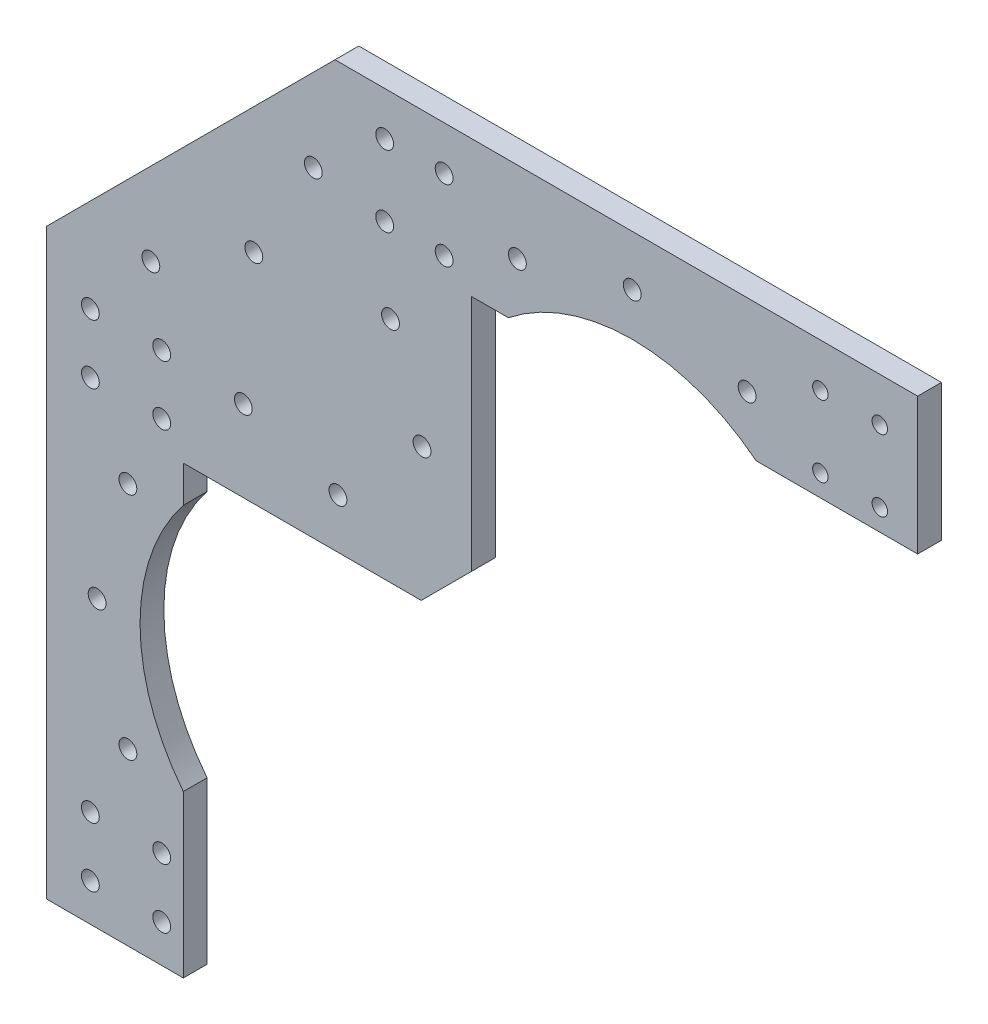
SolidWorks part; units mm, degrees
ref_plane "Front Plane" through (0, 0, 0) normal (0, 0, 1) x (1, 0, 0)
ref_plane "Top Plane" through (0, 0, 0) normal (0, 1, 0) x (1, 0, 0)
ref_plane "Right Plane" through (0, 0, 0) normal (1, 0, 0) x (0, 0, -1)
sketch "Sketch1" plane through (0, 0, 0) normal (0, 0, 1) x (1, 0, 0)
  line L0 (0, 0) -> (0, 75.5) construction
  line L1 (-98.5, -48) -> (-75.5, -48)
  line L2 (-98.5, -48) -> (-98.5, 49.9924)
  line L4 (-75.5, -48) -> (-75.5, 27) construction
  line L5 (-49.9924, 98.5) -> (48, 98.5)
  line L7 (-27, 75.5) -> (48, 75.5) construction
  line L8 (48, 98.5) -> (48, 75.5)
  line L9 (0, 0) -> (-75.5, 0) construction
  line L10 (-27, 75.5) -> (-75.5, 27) construction
  line L11 (-75.5, 75.5) -> (-27, 75.5) construction
  line L12 (-75.5, 27) -> (-75.5, 75.5) construction
  line L13 (-49.9924, 98.5) -> (-98.5, 49.9924)
  line L14 (-98.5, 98.5) -> (-49.9924, 98.5) construction
  line L15 (-98.5, 49.9924) -> (-98.5, 98.5) construction
  line L16 (-20.8425, 75.5) -> (-27, 75.5)
  line L17 (20.8425, 75.5) -> (48, 75.5)
  line L18 (-75.5, 27) -> (-75.5, 20.8425)
  line L19 (-75.5, -48) -> (-75.5, -20.8425)
  line L20 (-75.5, 20.8425) -> (-75.5, -20.8425) construction
  line L21 (-20.8425, 75.5) -> (20.8425, 75.5) construction
  line L22 (-75.5, 27) -> (-35.4853, 27)
  line L23 (-27, 35.4853) -> (-27, 75.5)
  line L24 (-35.4853, 27) -> (-27, 35.4853)
  arc A0 (20.8425, 75.5) -> (-20.8425, 75.5) centre (0, 49.3) ccw
  arc A1 (-75.5, 20.8425) -> (-75.5, -20.8425) centre (-49.3, 0) ccw
  point P16 (0, 0)
  dimension "D6" = 33.4791
  dimension "D1" = 135
  dimension "D2" = 23
  dimension "D3" = 75.5
  dimension "D4" = 48
  dimension "D8" = 27
  dimension "D9" = 12
  dimension "D5" = 97.9924
  dimension "D7" = 26.2
extrude "Boss-Extrude1" add sketch "Sketch1" along normal blind 4
ref_axis "Axis1" through (0, 0, -0.2) along (0, 0, 1)
sketch "Sketch3" plane through (0, 0, 4) normal (0, 0, 1) x (1, 0, 0)
  line L0 (-91.1351, 41.6359) -> (-91.1351, 31.6359) construction
  line L1 (-91.1351, -31.6359) -> (-91.1351, -41.6359) construction
  line L2 (-91.1351, -31.6359) -> (-79.1351, -31.6359) construction
  line L3 (-79.1351, -31.6359) -> (-79.1351, -41.6359) construction
  line L4 (-91.1351, -41.6359) -> (-79.1351, -41.6359) construction
  line L5 (-91.1351, 41.6359) -> (-79.1351, 41.6359) construction
  line L6 (-79.1351, 41.6359) -> (-79.1351, 31.6359) construction
  line L7 (-91.1351, 31.6359) -> (-79.1351, 31.6359) construction
  line L8 (31.6359, 91.1351) -> (31.6359, 79.1351) construction
  line L9 (31.6359, 91.1351) -> (41.6359, 91.1351) construction
  line L10 (41.6359, 91.1351) -> (41.6359, 79.1351) construction
  line L11 (31.6359, 79.1351) -> (41.6359, 79.1351) construction
  line L12 (-31.6359, 91.1351) -> (-31.6359, 79.1351) construction
  line L13 (-31.6359, 91.1351) -> (-41.6359, 91.1351) construction
  line L14 (-41.6359, 91.1351) -> (-41.6359, 79.1351) construction
  line L15 (-31.6359, 79.1351) -> (-41.6359, 79.1351) construction
  line L16 (-79.1351, 31.6359) -> (-79.1351, 0) construction
  line L17 (-79.1351, 0) -> (0, 0) construction
  line L18 (-79.1351, 0) -> (-79.1351, -31.6359) construction
  line L19 (0, 79.1351) -> (0, 0) construction
  line L20 (-31.6359, 79.1351) -> (0, 79.1351) construction
  line L21 (0, 79.1351) -> (31.6359, 79.1351) construction
  circle A0 centre (-91.1351, -41.6359) radius 1.5
  circle A1 centre (-91.1351, -31.6359) radius 1.5
  circle A2 centre (-79.1351, -31.6359) radius 1.5
  circle A3 centre (-79.1351, -41.6359) radius 1.5
  circle A4 centre (-91.1351, 31.6359) radius 1.5
  circle A5 centre (-91.1351, 41.6359) radius 1.5
  circle A6 centre (-79.1351, 41.6359) radius 1.5
  circle A7 centre (-79.1351, 31.6359) radius 1.5
  circle A8 centre (31.6359, 79.1351) radius 1.3
  circle A9 centre (31.6359, 91.1351) radius 1.3
  circle A10 centre (41.6359, 91.1351) radius 1.3
  circle A11 centre (41.6359, 79.1351) radius 1.3
  circle A12 centre (-31.6359, 79.1351) radius 1.5
  circle A13 centre (-31.6359, 91.1351) radius 1.5
  circle A14 centre (-41.6359, 91.1351) radius 1.5
  circle A15 centre (-41.6359, 79.1351) radius 1.5
  point P15 (0, 0)
  point P44 (0, 0)
  point P45 (0, 0)
  point P46 (0, 0)
  point P47 (0, 0)
  point P48 (-0.9577, 0)
  point P49 (0, 0)
  dimension "D1" = 3
  dimension "D2" = 3
  dimension "D3" = 2.6
  dimension "D4" = 3
  dimension "D5" = 79.1351
  dimension "D6" = 12
  dimension "D7" = 10
  dimension "D8" = 31.6359
extrude "Cut-Extrude1" cut sketch "Sketch3" against normal blind 10
sketch "Sketch4" plane through (0, 0, 4) normal (0, 0, 1) x (1, 0, 0)
  line L0 (0, 0) -> (0, 90) construction
  line L1 (0, 0) -> (-63.6396, 63.6396) construction
  line L2 (0, 0) -> (-90, 0) construction
  line L3 (-84.8236, 19.3185) -> (-90, 0) construction
  line L4 (-90, 0) -> (-84.8236, -19.3185) construction
  line L5 (-80.9601, 53.6396) -> (-63.6396, 63.6396) construction
  line L6 (-63.6396, 63.6396) -> (-83.2677, 83.2677) construction
  line L7 (-19.3185, 84.8236) -> (0, 90) construction
  line L8 (-65.4074, 40.6586) -> (-40.6586, 65.4074) construction
  line L9 (-35.3553, 49.4975) -> (-49.4975, 35.3553) construction
  line L10 (-75.5, -48) -> (-75.5, -20.8425) construction
  line L11 (-35.4853, 27) -> (-27, 35.4853) construction
  circle A0 centre (-90, 0) radius 1.5
  circle A1 centre (-63.6396, 63.6396) radius 1.5
  circle A2 centre (0, 90) radius 1.5
  circle A3 centre (-80.9601, 53.6396) radius 1.5
  circle A4 centre (-53.6396, 80.9601) radius 1.5
  circle A5 centre (19.3185, 84.8236) radius 1.5
  circle A6 centre (-19.3185, 84.8236) radius 1.5
  circle A7 centre (-84.8236, 19.3185) radius 1.5
  circle A8 centre (-84.8236, -19.3185) radius 1.5
  circle A9 centre (-40.6586, 65.4074) radius 1.5
  circle A10 centre (-65.4074, 40.6586) radius 1.5
  circle A11 centre (-49.4975, 35.3553) radius 1.5
  circle A12 centre (-35.3553, 49.4975) radius 1.5
  point P33 (-83.2677, 83.2677)
  dimension "D2" = 3
  dimension "D1" = 45
  dimension "D3" = 14.5
  dimension "D4" = 75
  dimension "D5" = 20
  dimension "D6" = 45.8162
  dimension "D7" = 75
  dimension "D8" = 75
  dimension "D9" = 35
  dimension "D10" = 20
  dimension "D11" = 15
  dimension "D12" = 15
extrude "Cut-Extrude2" cut sketch "Sketch4" against normal through all
equation "\"EyeDiameter\" = 35"
equation "\"BasePlaneDistance\" = \"EyeDiameter\"/2+19.84"
equation "\"EyeClearance\" = 2"
equation "\"L2Thickness\" = 8"
equation "\"L2_ID\" = 20"
equation "\"D3@Sketch1\"= \"BasePlaneDistance\" + 38.16"
equation "\"D5@Sketch3\"=\"BasePlaneDistance\" + 41.79513322"
